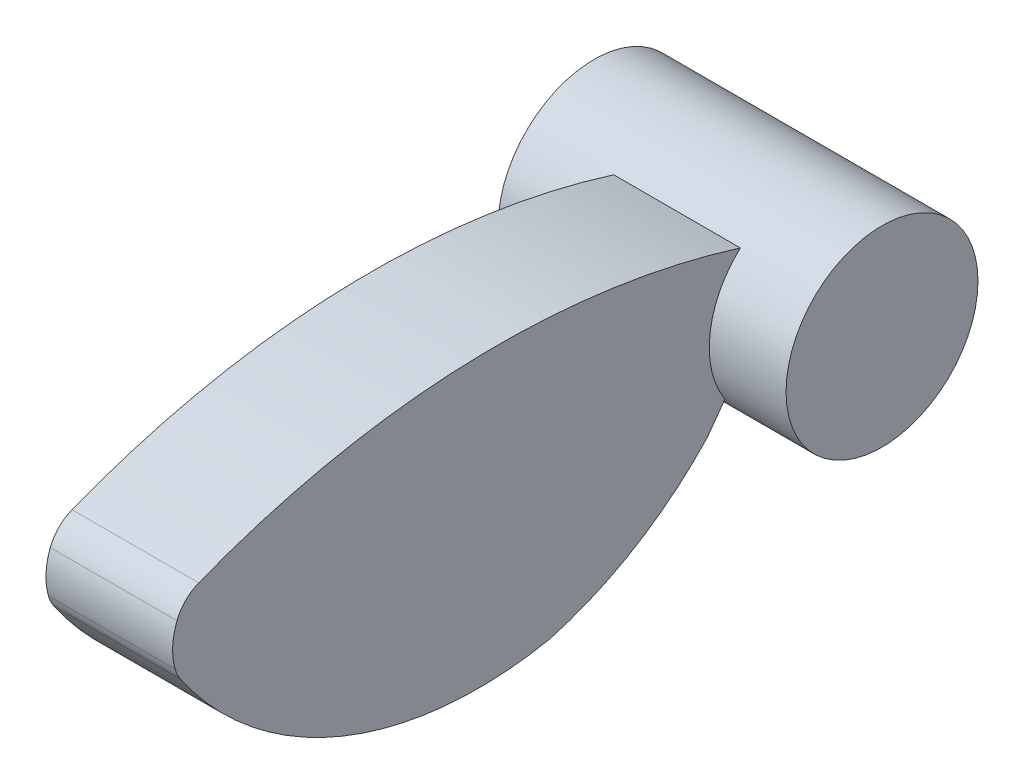
SolidWorks part; units mm, degrees
ref_plane "Front Plane" through (0, 0, 0) normal (0, 0, 1) x (1, 0, 0)
ref_plane "Top Plane" through (0, 0, 0) normal (0, 1, 0) x (1, 0, 0)
ref_plane "Right Plane" through (0, 0, 0) normal (1, 0, 0) x (0, 0, -1)
sketch "Sketch1" plane through (0, 0, 0) normal (1, 0, 0) x (0, 0, -1)
  circle A0 centre (0, 0) radius 6.35
  dimension "D1" = 12.7
extrude "Boss-Extrude1" add sketch "Sketch1" along normal blind 8.382
sketch "Sketch6" plane through (0, 0, 0) normal (0, 0, 1) x (1, 0, 0)
  line L1 (0, 5.08) -> (8.382, 5.08)
  line L2 (0, 5.08) -> (0, -5.08)
  line L3 (0, -5.08) -> (8.382, -5.08)
  line L4 (8.382, 5.08) -> (8.382, -5.08)
  line L5 (0, 6.35) -> (0, -6.35) construction
  line L6 (8.382, -6.35) -> (8.382, 6.35) construction
  dimension "D1" = 0
  dimension "D2" = 0
  dimension "D3" = 5.08
  dimension "D4" = 10.16
extrude "Boss-Extrude2" add sketch "Sketch6" along normal blind 31.75
sketch "Sketch5" plane through (0, 0, 0) normal (0, 1, 0) x (1, 0, 0)
  line L1 (8.382, 12.7) -> (5.842, 12.7)
  line L2 (8.382, 12.7) -> (8.382, 0)
  line L3 (8.382, 0) -> (5.842, 0)
  line L4 (5.842, 12.7) -> (5.842, 0)
  line L5 (8.382, -3.81) -> (8.382, 6.35) construction
  dimension "D1" = 12.7
  dimension "D2" = 0
  dimension "D3" = 2.54
  dimension "D4" = 0
sketch "Sketch8" plane through (8.382, 0, 0) normal (1, 0, 0) x (0, 0, -1)
  arc A2 (-4.2921, 4.6797) -> (-5.2242, -3.6098) centre (0, 0) ccw
  arc A4 (-16.9092, -11.4257) -> (-41.526, -1.2198) centre (-21.6116, 12.0231) cw
  arc A5 (-4.2921, 4.6797) -> (-40.9154, 3.0883) centre (-20.4005, -46.8189) ccw
  arc A6 (-40.9154, 3.0883) -> (-41.526, -1.2198) centre (-37.5759, 0.4177) ccw
  arc A7 (-5.2242, -3.6098) -> (-16.9092, -11.4257) centre (-22.8963, 10.1679) cw
  arc A8 (-3.81, -5.08) -> (-3.81, 5.08) centre (0, 0) ccw construction
  arc A9 (-3.81, -5.08) -> (-3.81, 5.08) centre (0, 0) ccw construction
  point P2 (-2.7983, -5.08)
  point P14 (-3.4314, -5.343)
  point P18 (0, 0)
  point P20 (0, 0)
  point P21 (-3.81, -5.08)
  point P22 (-5.2242, -3.6098)
sketch "Sketch9" plane through (0, 0, 0) normal (-1, 0, 0) x (0, 0, 1)
  line L0 (31.75, -5.08) -> (3.81, -5.08) construction
  line L1 (31.75, 5.08) -> (11.4084, 5.08)
  line L2 (31.75, 5.08) -> (31.75, -5.08)
  line L3 (31.75, -5.08) -> (11.4084, -5.08)
  line L4 (11.4084, 0.9555) -> (11.4084, -5.08)
  line L5 (11.4084, 5.08) -> (3.81, 5.08)
  line L6 (6.0928, 0.9555) -> (11.4084, 0.9555)
  arc A0 (3.81, 5.08) -> (6.0928, 0.9555) centre (-0.3346, 0.0921) cw
extrude "Cut-Extrude4" cut sketch "Sketch9" against normal blind 37.592
extrude "Boss-Extrude3" add sketch "Sketch8" against normal up to surface (8.382 mm away) up to face at (0, -0.5908, 5.3515)
sketch "Sketch11" plane through (8.382, 0, 0) normal (1, 0, 0) x (0, 0, -1)
  circle A0 centre (0, 0) radius 6.35
extrude "Boss-Extrude4" add sketch "Sketch11" along normal blind 5.08 and the other way blind 13.97
fillet "Fillet1" radius 2.54 2 edges at (4.191, -1.2198, 41.526) (4.191, 3.0883, 40.9154)
sketch "Sketch12" plane through (0, 0, 0) normal (-1, 0, 0) x (0, 0, 1)
  line L0 (5.3113, -3.4802) -> (6.4759, -5.08)
  line L1 (6.4759, -5.08) -> (3.81, -5.08)
  arc A0 (3.81, -5.08) -> (5.3113, -3.4802) centre (0, 0) ccw
  arc A1 (3.81, -5.08) -> (4.2921, 4.6797) centre (0, 0) ccw construction
extrude "Cut-Extrude5" cut sketch "Sketch12" against normal blind 12.192
